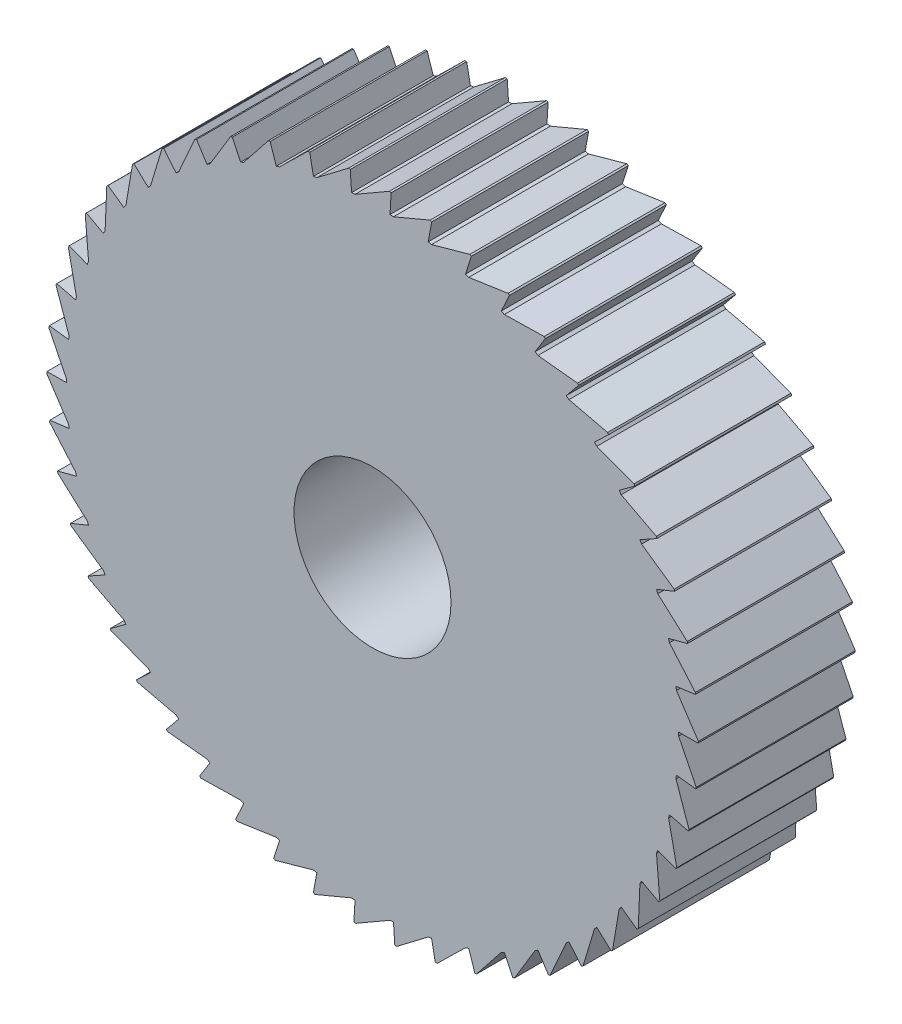
SolidWorks part; units mm, degrees
ref_plane "Front" through (0, 0, 0) normal (0, 0, 1) x (1, 0, 0)
ref_plane "Top" through (0, 0, 0) normal (0, 1, 0) x (1, 0, 0)
ref_plane "Right" through (0, 0, 0) normal (1, 0, 0) x (0, 0, -1)
sketch "Sketch1" plane through (0, 0, 0) normal (0, 0, 1) x (1, 0, 0)
  line L0 (-25, 0) -> (25, 0) construction
  line L1 (0, 0) -> (0, 1.6) construction
  circle A0 centre (0, 0) radius 25 construction
  circle A1 centre (0, 0) radius 1.5625 construction
  circle A2 centre (0, 0) radius 6
  circle A3 centre (0, 0) radius 23.4
  point P8 (0, 25)
  point P9 (0, -25)
  dimension "D1" = 46.8
  dimension "Tooth Depth" = 1.6
extrude "Boss-Extrude1" add sketch "Sketch1" against normal blind 12
sketch "Sketch2" plane through (0, 0, 0) normal (0, 0, 1) x (1, 0, 0)
  line L0 (0, 0) -> (0, 25) construction
  line L1 (0, 0) -> (-1.3376, 23.3617) construction
  line L2 (0, 0) -> (1.4291, 24.9591) construction
  line L3 (-1.3376, 23.3617) -> (1.3376, 23.3617) construction
  line L4 (-1.3376, 23.3617) -> (1.4291, 24.9591)
  line L5 (1.4291, 24.9591) -> (1.3376, 23.3617)
  circle A0 centre (0, 0) radius 25 construction
  circle A2 centre (0, 0) radius 23.4 construction
  arc A4 (1.3376, 23.3617) -> (-1.3376, 23.3617) centre (0, 0) ccw
  point P8 (0, 23.3617)
  dimension "D1" = 60
extrude "Boss-Extrude2" add sketch "Sketch2" against normal blind 12
chamfer "Chamfer2" distance 0.16 angle 45 1 edges at (1.4291, 24.9591, -6) first distance on face at (0.0457, 24.1604, -6)
pattern_circular "CirPattern1" count 50 over 360 about axis through (0, 0, -12) along (0, 0, 1) of "Boss-Extrude2", "Chamfer2"
sketch "Pawl" plane through (0, 0, 0) normal (0, 0, 1) x (1, 0, 0)
  line L0 (4.0474, 30.5) -> (39.5474, 30.5) construction
  line L1 (0.5474, 27) -> (0.5474, 24.9793) construction
  line L2 (0.5474, 24.9793) -> (4.0474, 27) construction
  line L3 (49.5474, -6.5226) -> (49.5474, 49.6734) construction
  arc A0 (34.244, 16.5106) -> (39.5474, 30.5) centre (39.5474, 22.5) ccw construction
  arc A1 (4.0474, 30.5) -> (0.5474, 27) centre (4.0474, 27) ccw construction
  circle A2 centre (39.5474, 22.5) radius 4 construction
  arc A3 (34.244, 16.5106) -> (4.0474, 27) centre (6.4009, -14.934) ccw construction
  point P6 (47.5474, 22.5)
  point P18 (47.5474, 22.5)
  dimension "D3" = 42
  dimension "D2" = 3.5
  dimension "PawlK" = 8
  dimension "D4" = 8
  dimension "D1" = 60
  dimension "PawlN" = 49
  dimension "PawlM" = 39
  dimension "Mounting Distance" = 45.5
  dimension "Center Distance" = 22.5
sketch "Sketch3" plane through (0, 0, 0) normal (1, 0, 0) x (0, 0, -1)
  line L0 (0, -6) -> (12, -6) construction
  line L1 (12, 6) -> (0, 6) construction
  line L2 (0, -6) -> (12, -6) construction
  line L3 (12, 6) -> (0, 6) construction
ref_plane "Contact Plane 1" through (0, 0, 0) normal (0, 0, 1) x (1, 0, 0)
ref_plane "Contact Plane 2" through (0, 0, -12) normal (0, 0, -1) x (-1, 0, 0)
ref_axis "Center Axis 1" through (0, 0, -12) along (0, 0, 1)
equation "\"Pitch Dia@Sketch1\" = \"Teeth@Sketch1\"/16"
equation "\"D1@Boss-Extrude2\" = \"D1@Boss-Extrude1\""
equation "\"D1@CirPattern1\" = \"Teeth@Sketch1\""
equation "\"D1@Sketch1\"=\"OD@Sketch1\"-2*\"Tooth Depth@Sketch1\""
equation "\"D1@Chamfer2\"=\"Tooth Depth@Sketch1\"/10"
